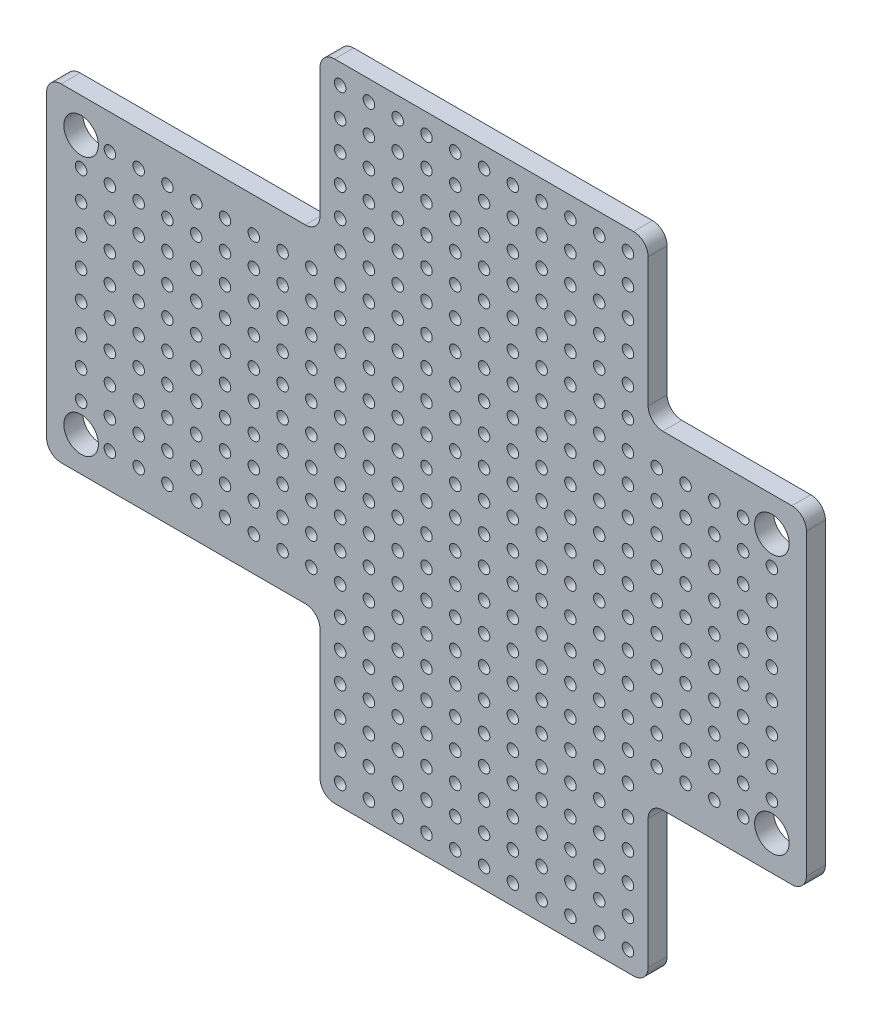
SolidWorks part; units mm, degrees
ref_plane "Front Plane" through (0, 0, 0) normal (0, 0, 1) x (1, 0, 0)
ref_plane "Top Plane" through (0, 0, 0) normal (0, 1, 0) x (1, 0, 0)
ref_plane "Right Plane" through (0, 0, 0) normal (1, 0, 0) x (0, 0, -1)
sketch "Sketch1" plane through (0, 0, 0) normal (0, 0, 1) x (1, 0, 0)
  line L0 (0, 14.25) -> (76, 14.25) construction
  line L1 (0, 0) -> (23.75, 0)
  line L2 (0, 0) -> (0, 28.5)
  line L3 (0, 28.5) -> (23.75, 28.5)
  line L4 (66, 0) -> (66, 28.5)
  line L5 (38, -42.734) -> (38, 127.234) construction
  line L6 (0, 25.5) -> (76, 25.5) construction
  line L7 (76, 3) -> (0, 3) construction
  line L8 (63, 0) -> (63, 28.5) construction
  line L9 (3, 0) -> (3, 28.5) construction
  line L12 (23.75, 28.5) -> (23.75, 42.25)
  line L13 (23.75, 42.25) -> (52.25, 42.25)
  line L14 (52.25, 42.25) -> (52.25, 28.5)
  line L15 (52.25, -13.75) -> (52.25, 0)
  line L16 (23.75, -13.75) -> (52.25, -13.75)
  line L17 (23.75, 0) -> (23.75, -13.75)
  line L18 (52.25, 28.5) -> (66, 28.5)
  line L19 (52.25, 0) -> (66, 0)
  line L20 (25.5, 25.5) -> (25.5, 28) construction
  circle A0 centre (3, 25.5) radius 1.5
  circle A1 centre (63, 25.5) radius 1.5
  circle A2 centre (3, 3) radius 1.5
  circle A3 centre (63, 3) radius 1.5
  circle A4 centre (55.5, 5.5) radius 0.5
  circle A5 centre (5.5, 3) radius 0.5
  circle A6 centre (8, 3) radius 0.5
  circle A7 centre (10.5, 3) radius 0.5
  circle A8 centre (13, 3) radius 0.5
  circle A9 centre (15.5, 3) radius 0.5
  circle A10 centre (18, 3) radius 0.5
  circle A11 centre (20.5, 3) radius 0.5
  circle A12 centre (23, 3) radius 0.5
  circle A13 centre (25.5, 3) radius 0.5
  circle A14 centre (28, 3) radius 0.5
  circle A15 centre (30.5, 3) radius 0.5
  circle A16 centre (33, 3) radius 0.5
  circle A17 centre (35.5, 3) radius 0.5
  circle A18 centre (38, 3) radius 0.5
  circle A19 centre (40.5, 3) radius 0.5
  circle A20 centre (43, 3) radius 0.5
  circle A21 centre (45.5, 3) radius 0.5
  circle A22 centre (48, 3) radius 0.5
  circle A23 centre (50.5, 3) radius 0.5
  circle A24 centre (55.5, 10.5) radius 0.5
  circle A25 centre (55.5, 8) radius 0.5
  circle A26 centre (55.5, 15.5) radius 0.5
  circle A27 centre (55.5, 18) radius 0.5
  circle A28 centre (55.5, 20.5) radius 0.5
  circle A29 centre (55.5, 23) radius 0.5
  circle A30 centre (53, 3) radius 0.5
  circle A31 centre (53, 25.5) radius 0.5
  circle A32 centre (58, 5.5) radius 0.5
  circle A33 centre (5.5, 5.5) radius 0.5
  circle A34 centre (8, 5.5) radius 0.5
  circle A35 centre (10.5, 5.5) radius 0.5
  circle A36 centre (13, 5.5) radius 0.5
  circle A37 centre (15.5, 5.5) radius 0.5
  circle A38 centre (18, 5.5) radius 0.5
  circle A39 centre (20.5, 5.5) radius 0.5
  circle A40 centre (23, 5.5) radius 0.5
  circle A41 centre (25.5, 5.5) radius 0.5
  circle A42 centre (28, 5.5) radius 0.5
  circle A43 centre (30.5, 5.5) radius 0.5
  circle A44 centre (33, 5.5) radius 0.5
  circle A45 centre (35.5, 5.5) radius 0.5
  circle A46 centre (38, 5.5) radius 0.5
  circle A47 centre (40.5, 5.5) radius 0.5
  circle A48 centre (43, 5.5) radius 0.5
  circle A49 centre (45.5, 5.5) radius 0.5
  circle A50 centre (48, 5.5) radius 0.5
  circle A51 centre (50.5, 5.5) radius 0.5
  circle A52 centre (53, 5.5) radius 0.5
  circle A53 centre (58, 10.5) radius 0.5
  circle A54 centre (58, 8) radius 0.5
  circle A55 centre (58, 15.5) radius 0.5
  circle A56 centre (58, 18) radius 0.5
  circle A57 centre (58, 20.5) radius 0.5
  circle A58 centre (58, 23) radius 0.5
  circle A59 centre (55.5, 3) radius 0.5
  circle A60 centre (55.5, 25.5) radius 0.5
  circle A61 centre (5.5, 8) radius 0.5
  circle A62 centre (8, 8) radius 0.5
  circle A63 centre (10.5, 8) radius 0.5
  circle A64 centre (13, 8) radius 0.5
  circle A65 centre (15.5, 8) radius 0.5
  circle A66 centre (18, 8) radius 0.5
  circle A67 centre (20.5, 8) radius 0.5
  circle A68 centre (23, 8) radius 0.5
  circle A69 centre (25.5, 8) radius 0.5
  circle A70 centre (28, 8) radius 0.5
  circle A71 centre (30.5, 8) radius 0.5
  circle A72 centre (33, 8) radius 0.5
  circle A73 centre (35.5, 8) radius 0.5
  circle A74 centre (38, 8) radius 0.5
  circle A75 centre (40.5, 8) radius 0.5
  circle A76 centre (43, 8) radius 0.5
  circle A77 centre (45.5, 8) radius 0.5
  circle A78 centre (48, 8) radius 0.5
  circle A79 centre (50.5, 8) radius 0.5
  circle A80 centre (53, 8) radius 0.5
  circle A81 centre (60.5, 5.5) radius 0.5
  circle A82 centre (60.5, 10.5) radius 0.5
  circle A83 centre (60.5, 8) radius 0.5
  circle A84 centre (60.5, 15.5) radius 0.5
  circle A85 centre (60.5, 18) radius 0.5
  circle A86 centre (60.5, 20.5) radius 0.5
  circle A87 centre (60.5, 23) radius 0.5
  circle A88 centre (58, 3) radius 0.5
  circle A89 centre (5.5, 10.5) radius 0.5
  circle A90 centre (8, 10.5) radius 0.5
  circle A91 centre (10.5, 10.5) radius 0.5
  circle A92 centre (13, 10.5) radius 0.5
  circle A93 centre (15.5, 10.5) radius 0.5
  circle A94 centre (18, 10.5) radius 0.5
  circle A95 centre (20.5, 10.5) radius 0.5
  circle A96 centre (23, 10.5) radius 0.5
  circle A97 centre (25.5, 10.5) radius 0.5
  circle A98 centre (28, 10.5) radius 0.5
  circle A99 centre (30.5, 10.5) radius 0.5
  circle A100 centre (33, 10.5) radius 0.5
  circle A101 centre (35.5, 10.5) radius 0.5
  circle A102 centre (38, 10.5) radius 0.5
  circle A103 centre (40.5, 10.5) radius 0.5
  circle A104 centre (43, 10.5) radius 0.5
  circle A105 centre (45.5, 10.5) radius 0.5
  circle A106 centre (48, 10.5) radius 0.5
  circle A107 centre (50.5, 10.5) radius 0.5
  circle A108 centre (53, 10.5) radius 0.5
  circle A109 centre (58, 25.5) radius 0.5
  circle A110 centre (63, 5.5) radius 0.5
  circle A111 centre (63, 10.5) radius 0.5
  circle A112 centre (63, 8) radius 0.5
  circle A113 centre (63, 15.5) radius 0.5
  circle A114 centre (63, 18) radius 0.5
  circle A115 centre (63, 20.5) radius 0.5
  circle A116 centre (63, 23) radius 0.5
  circle A117 centre (5.5, 13) radius 0.5
  circle A118 centre (8, 13) radius 0.5
  circle A119 centre (10.5, 13) radius 0.5
  circle A120 centre (13, 13) radius 0.5
  circle A121 centre (15.5, 13) radius 0.5
  circle A122 centre (18, 13) radius 0.5
  circle A123 centre (20.5, 13) radius 0.5
  circle A124 centre (23, 13) radius 0.5
  circle A125 centre (25.5, 13) radius 0.5
  circle A126 centre (28, 13) radius 0.5
  circle A127 centre (30.5, 13) radius 0.5
  circle A128 centre (33, 13) radius 0.5
  circle A129 centre (35.5, 13) radius 0.5
  circle A130 centre (38, 13) radius 0.5
  circle A131 centre (40.5, 13) radius 0.5
  circle A132 centre (43, 13) radius 0.5
  circle A133 centre (45.5, 13) radius 0.5
  circle A134 centre (48, 13) radius 0.5
  circle A135 centre (50.5, 13) radius 0.5
  circle A136 centre (53, 13) radius 0.5
  circle A137 centre (60.5, 3) radius 0.5
  circle A138 centre (60.5, 25.5) radius 0.5
  circle A139 centre (55.5, 13) radius 0.5
  circle A140 centre (58, 13) radius 0.5
  circle A141 centre (60.5, 13) radius 0.5
  circle A142 centre (63, 13) radius 0.5
  circle A145 centre (5.5, 15.5) radius 0.5
  circle A146 centre (8, 15.5) radius 0.5
  circle A147 centre (10.5, 15.5) radius 0.5
  circle A148 centre (13, 15.5) radius 0.5
  circle A149 centre (15.5, 15.5) radius 0.5
  circle A150 centre (18, 15.5) radius 0.5
  circle A151 centre (20.5, 15.5) radius 0.5
  circle A152 centre (23, 15.5) radius 0.5
  circle A153 centre (25.5, 15.5) radius 0.5
  circle A154 centre (28, 15.5) radius 0.5
  circle A155 centre (30.5, 15.5) radius 0.5
  circle A156 centre (33, 15.5) radius 0.5
  circle A157 centre (35.5, 15.5) radius 0.5
  circle A158 centre (38, 15.5) radius 0.5
  circle A159 centre (40.5, 15.5) radius 0.5
  circle A160 centre (43, 15.5) radius 0.5
  circle A161 centre (45.5, 15.5) radius 0.5
  circle A162 centre (48, 15.5) radius 0.5
  circle A163 centre (50.5, 15.5) radius 0.5
  circle A164 centre (53, 15.5) radius 0.5
  circle A173 centre (5.5, 18) radius 0.5
  circle A174 centre (8, 18) radius 0.5
  circle A175 centre (10.5, 18) radius 0.5
  circle A176 centre (13, 18) radius 0.5
  circle A177 centre (15.5, 18) radius 0.5
  circle A178 centre (18, 18) radius 0.5
  circle A179 centre (20.5, 18) radius 0.5
  circle A180 centre (23, 18) radius 0.5
  circle A181 centre (25.5, 18) radius 0.5
  circle A182 centre (28, 18) radius 0.5
  circle A183 centre (30.5, 18) radius 0.5
  circle A184 centre (33, 18) radius 0.5
  circle A185 centre (35.5, 18) radius 0.5
  circle A186 centre (38, 18) radius 0.5
  circle A187 centre (40.5, 18) radius 0.5
  circle A188 centre (43, 18) radius 0.5
  circle A189 centre (45.5, 18) radius 0.5
  circle A190 centre (48, 18) radius 0.5
  circle A191 centre (50.5, 18) radius 0.5
  circle A192 centre (53, 18) radius 0.5
  circle A201 centre (5.5, 20.5) radius 0.5
  circle A202 centre (8, 20.5) radius 0.5
  circle A203 centre (10.5, 20.5) radius 0.5
  circle A204 centre (13, 20.5) radius 0.5
  circle A205 centre (15.5, 20.5) radius 0.5
  circle A206 centre (18, 20.5) radius 0.5
  circle A207 centre (20.5, 20.5) radius 0.5
  circle A208 centre (23, 20.5) radius 0.5
  circle A209 centre (25.5, 20.5) radius 0.5
  circle A210 centre (28, 20.5) radius 0.5
  circle A211 centre (30.5, 20.5) radius 0.5
  circle A212 centre (33, 20.5) radius 0.5
  circle A213 centre (35.5, 20.5) radius 0.5
  circle A214 centre (38, 20.5) radius 0.5
  circle A215 centre (40.5, 20.5) radius 0.5
  circle A216 centre (43, 20.5) radius 0.5
  circle A217 centre (45.5, 20.5) radius 0.5
  circle A218 centre (48, 20.5) radius 0.5
  circle A219 centre (50.5, 20.5) radius 0.5
  circle A220 centre (53, 20.5) radius 0.5
  circle A229 centre (5.5, 23) radius 0.5
  circle A230 centre (8, 23) radius 0.5
  circle A231 centre (10.5, 23) radius 0.5
  circle A232 centre (13, 23) radius 0.5
  circle A233 centre (15.5, 23) radius 0.5
  circle A234 centre (18, 23) radius 0.5
  circle A235 centre (20.5, 23) radius 0.5
  circle A236 centre (23, 23) radius 0.5
  circle A237 centre (25.5, 23) radius 0.5
  circle A238 centre (28, 23) radius 0.5
  circle A239 centre (30.5, 23) radius 0.5
  circle A240 centre (33, 23) radius 0.5
  circle A241 centre (35.5, 23) radius 0.5
  circle A242 centre (38, 23) radius 0.5
  circle A243 centre (40.5, 23) radius 0.5
  circle A244 centre (43, 23) radius 0.5
  circle A245 centre (45.5, 23) radius 0.5
  circle A246 centre (48, 23) radius 0.5
  circle A247 centre (50.5, 23) radius 0.5
  circle A248 centre (53, 23) radius 0.5
  circle A257 centre (5.5, 25.5) radius 0.5
  circle A258 centre (8, 25.5) radius 0.5
  circle A259 centre (10.5, 25.5) radius 0.5
  circle A260 centre (13, 25.5) radius 0.5
  circle A261 centre (15.5, 25.5) radius 0.5
  circle A262 centre (18, 25.5) radius 0.5
  circle A263 centre (20.5, 25.5) radius 0.5
  circle A264 centre (23, 25.5) radius 0.5
  circle A265 centre (25.5, 25.5) radius 0.5
  circle A266 centre (28, 25.5) radius 0.5
  circle A267 centre (30.5, 25.5) radius 0.5
  circle A268 centre (33, 25.5) radius 0.5
  circle A269 centre (35.5, 25.5) radius 0.5
  circle A270 centre (38, 25.5) radius 0.5
  circle A271 centre (40.5, 25.5) radius 0.5
  circle A272 centre (43, 25.5) radius 0.5
  circle A273 centre (45.5, 25.5) radius 0.5
  circle A274 centre (48, 25.5) radius 0.5
  circle A275 centre (50.5, 25.5) radius 0.5
  circle A285 centre (3, 5.5) radius 0.5
  circle A286 centre (3, 8) radius 0.5
  circle A287 centre (3, 10.5) radius 0.5
  circle A288 centre (3, 13) radius 0.5
  circle A289 centre (3, 15.5) radius 0.5
  circle A290 centre (3, 18) radius 0.5
  circle A291 centre (3, 20.5) radius 0.5
  circle A292 centre (3, 23) radius 0.5
  circle A294 centre (25.5, 28) radius 0.5
  circle A295 centre (28, 28) radius 0.5
  circle A296 centre (30.5, 28) radius 0.5
  circle A297 centre (33, 28) radius 0.5
  circle A298 centre (35.5, 28) radius 0.5
  circle A299 centre (38, 28) radius 0.5
  circle A300 centre (40.5, 28) radius 0.5
  circle A301 centre (43, 28) radius 0.5
  circle A302 centre (45.5, 28) radius 0.5
  circle A303 centre (48, 28) radius 0.5
  circle A304 centre (50.5, 28) radius 0.5
  circle A305 centre (25.5, 30.5) radius 0.5
  circle A306 centre (28, 30.5) radius 0.5
  circle A307 centre (30.5, 30.5) radius 0.5
  circle A308 centre (33, 30.5) radius 0.5
  circle A309 centre (35.5, 30.5) radius 0.5
  circle A310 centre (38, 30.5) radius 0.5
  circle A311 centre (40.5, 30.5) radius 0.5
  circle A312 centre (43, 30.5) radius 0.5
  circle A313 centre (45.5, 30.5) radius 0.5
  circle A314 centre (48, 30.5) radius 0.5
  circle A315 centre (50.5, 30.5) radius 0.5
  circle A316 centre (25.5, 33) radius 0.5
  circle A317 centre (28, 33) radius 0.5
  circle A318 centre (30.5, 33) radius 0.5
  circle A319 centre (33, 33) radius 0.5
  circle A320 centre (35.5, 33) radius 0.5
  circle A321 centre (38, 33) radius 0.5
  circle A322 centre (40.5, 33) radius 0.5
  circle A323 centre (43, 33) radius 0.5
  circle A324 centre (45.5, 33) radius 0.5
  circle A325 centre (48, 33) radius 0.5
  circle A326 centre (50.5, 33) radius 0.5
  circle A327 centre (25.5, 35.5) radius 0.5
  circle A328 centre (28, 35.5) radius 0.5
  circle A329 centre (30.5, 35.5) radius 0.5
  circle A330 centre (33, 35.5) radius 0.5
  circle A331 centre (35.5, 35.5) radius 0.5
  circle A332 centre (38, 35.5) radius 0.5
  circle A333 centre (40.5, 35.5) radius 0.5
  circle A334 centre (43, 35.5) radius 0.5
  circle A335 centre (45.5, 35.5) radius 0.5
  circle A336 centre (48, 35.5) radius 0.5
  circle A337 centre (50.5, 35.5) radius 0.5
  circle A338 centre (25.5, 38) radius 0.5
  circle A339 centre (28, 38) radius 0.5
  circle A340 centre (30.5, 38) radius 0.5
  circle A341 centre (33, 38) radius 0.5
  circle A342 centre (35.5, 38) radius 0.5
  circle A343 centre (38, 38) radius 0.5
  circle A344 centre (40.5, 38) radius 0.5
  circle A345 centre (43, 38) radius 0.5
  circle A346 centre (45.5, 38) radius 0.5
  circle A347 centre (48, 38) radius 0.5
  circle A348 centre (50.5, 38) radius 0.5
  circle A349 centre (25.5, 40.5) radius 0.5
  circle A350 centre (28, 40.5) radius 0.5
  circle A351 centre (30.5, 40.5) radius 0.5
  circle A352 centre (33, 40.5) radius 0.5
  circle A353 centre (35.5, 40.5) radius 0.5
  circle A354 centre (38, 40.5) radius 0.5
  circle A355 centre (40.5, 40.5) radius 0.5
  circle A356 centre (43, 40.5) radius 0.5
  circle A357 centre (45.5, 40.5) radius 0.5
  circle A358 centre (48, 40.5) radius 0.5
  circle A359 centre (50.5, 40.5) radius 0.5
  circle A384 centre (25.5, -12) radius 0.5
  circle A385 centre (25.5, -9.5) radius 0.5
  circle A386 centre (25.5, -7) radius 0.5
  circle A387 centre (25.5, -4.5) radius 0.5
  circle A388 centre (25.5, -2) radius 0.5
  circle A389 centre (25.5, 0.5) radius 0.5
  circle A410 centre (50.5, -12) radius 0.5
  circle A411 centre (48, -12) radius 0.5
  circle A412 centre (45.5, -12) radius 0.5
  circle A413 centre (43, -12) radius 0.5
  circle A414 centre (40.5, -12) radius 0.5
  circle A415 centre (38, -12) radius 0.5
  circle A416 centre (35.5, -12) radius 0.5
  circle A417 centre (33, -12) radius 0.5
  circle A418 centre (30.5, -12) radius 0.5
  circle A419 centre (28, -12) radius 0.5
  circle A420 centre (50.5, -9.5) radius 0.5
  circle A421 centre (48, -9.5) radius 0.5
  circle A422 centre (45.5, -9.5) radius 0.5
  circle A423 centre (43, -9.5) radius 0.5
  circle A424 centre (40.5, -9.5) radius 0.5
  circle A425 centre (38, -9.5) radius 0.5
  circle A426 centre (35.5, -9.5) radius 0.5
  circle A427 centre (33, -9.5) radius 0.5
  circle A428 centre (30.5, -9.5) radius 0.5
  circle A429 centre (28, -9.5) radius 0.5
  circle A430 centre (50.5, -7) radius 0.5
  circle A431 centre (48, -7) radius 0.5
  circle A432 centre (45.5, -7) radius 0.5
  circle A433 centre (43, -7) radius 0.5
  circle A434 centre (40.5, -7) radius 0.5
  circle A435 centre (38, -7) radius 0.5
  circle A436 centre (35.5, -7) radius 0.5
  circle A437 centre (33, -7) radius 0.5
  circle A438 centre (30.5, -7) radius 0.5
  circle A439 centre (28, -7) radius 0.5
  circle A440 centre (50.5, -4.5) radius 0.5
  circle A441 centre (48, -4.5) radius 0.5
  circle A442 centre (45.5, -4.5) radius 0.5
  circle A443 centre (43, -4.5) radius 0.5
  circle A444 centre (40.5, -4.5) radius 0.5
  circle A445 centre (38, -4.5) radius 0.5
  circle A446 centre (35.5, -4.5) radius 0.5
  circle A447 centre (33, -4.5) radius 0.5
  circle A448 centre (30.5, -4.5) radius 0.5
  circle A449 centre (28, -4.5) radius 0.5
  circle A450 centre (50.5, -2) radius 0.5
  circle A451 centre (48, -2) radius 0.5
  circle A452 centre (45.5, -2) radius 0.5
  circle A453 centre (43, -2) radius 0.5
  circle A454 centre (40.5, -2) radius 0.5
  circle A455 centre (38, -2) radius 0.5
  circle A456 centre (35.5, -2) radius 0.5
  circle A457 centre (33, -2) radius 0.5
  circle A458 centre (30.5, -2) radius 0.5
  circle A459 centre (28, -2) radius 0.5
  circle A460 centre (50.5, 0.5) radius 0.5
  circle A461 centre (48, 0.5) radius 0.5
  circle A462 centre (45.5, 0.5) radius 0.5
  circle A463 centre (43, 0.5) radius 0.5
  circle A464 centre (40.5, 0.5) radius 0.5
  circle A465 centre (38, 0.5) radius 0.5
  circle A466 centre (35.5, 0.5) radius 0.5
  circle A467 centre (33, 0.5) radius 0.5
  circle A468 centre (30.5, 0.5) radius 0.5
  circle A469 centre (28, 0.5) radius 0.5
  circle A571 centre (3, 3) radius 1.5 [skipped]
  point P611 (38, 42.25)
  point P612 (38, 14.25)
  dimension "D3" = 3
  dimension "D8" = 3
  dimension "D9" = 11.25
  dimension "D10" = 38
  dimension "D11" = 35
  dimension "D1" = 28.5
  dimension "D2" = 3
  dimension "D4" = 3
  dimension "D5" = 3
  dimension "D13" = 5
  dimension "D14" = 5
  dimension "D16" = 28.5
  dimension "D17" = 13.75
  dimension "D19" = 2.5
  dimension "D12" = 13.75
  dimension "D6" = 2
  dimension "D7" = 2
  dimension "D18" = 7
extrude "Boss-Extrude1" add sketch "Sketch1" along normal blind 1.651
fillet "Fillet1" radius 1.27 12 edges at (0, 28.5, 0.8255) (0, 0, 0.8255) (52.25, 42.25, 0.8255) (23.75, 42.25, 0.8255) (23.75, 28.5, 0.8255) (23.75, 0, 0.8255) (23.75, -13.75, 0.8255) (52.25, -13.75, 0.8255) (52.25, 28.5, 0.8255) (52.25, 0, 0.8255) (66, 28.5, 0.8255) (66, 0, 0.8255)
ref_plane "Plane1" through (0, 14.25, 0) normal (0, -1, 0) x (1, 0, 0)
ref_plane "Plane2" through (38, 0, 0) normal (1, 0, 0) x (0, 0, -1)
